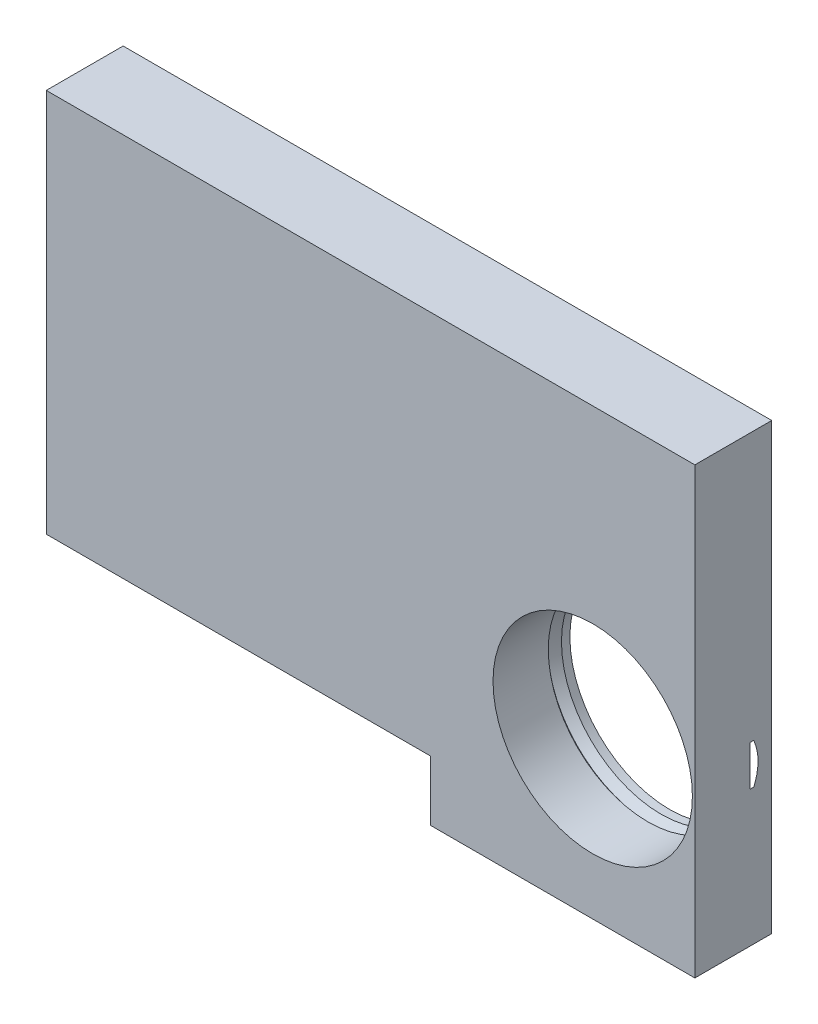
SolidWorks part; units mm, degrees
material "ABS"
ref_plane "Front Plane" through (0, 0, 0) normal (0, 0, 1) x (1, 0, 0)
ref_plane "Top Plane" through (0, 0, 0) normal (0, 1, 0) x (1, 0, 0)
ref_plane "Right Plane" through (0, 0, 0) normal (1, 0, 0) x (0, 0, -1)
sketch "Sketch1" plane through (0, 0, 17.5436) normal (0, 0, 1) x (1, 0, 0)
  line L0 (-2.5012, -56.5) -> (-2.5012, -59)
  line L1 (-2.5012, -59) -> (8.4988, -59)
  line L2 (8.4988, -59) -> (8.4988, -40.5)
  line L3 (8.4988, -40.5) -> (-2.5012, -40.5)
  line L4 (-2.5012, -40.5) -> (-18.5012, -40.5)
  line L5 (-18.5012, -40.5) -> (-18.5012, -56.5)
  line L6 (-18.5012, -56.5) -> (-2.5012, -56.5)
  line L7 (-2.5012, -56.5) -> (-2.5012, -40.5)
  line L8 (-2.5012, -40.5) -> (-18.5012, -40.5)
  line L9 (-18.5012, -40.5) -> (-18.5012, -56.5)
  line L10 (-18.5012, -56.5) -> (-2.5012, -56.5)
  line L11 (-2.5012, -56.5) -> (-2.5012, -40.5)
  circle A0 centre (4.2462, -52.5) radius 4 construction
  circle A1 centre (-6.5262, -52.475) radius 2.425 construction
  circle A2 centre (-6.5262, -44.525) radius 2.425 construction
  circle A3 centre (-14.4762, -44.525) radius 2.425 construction
  circle A4 centre (-14.4762, -52.475) radius 2.425 construction
  circle A5 centre (4.2462, -52.5) radius 4 construction
  circle A6 centre (-6.5262, -52.475) radius 2.425 construction
  circle A7 centre (-6.5262, -44.525) radius 2.425 construction
  circle A8 centre (-14.4762, -44.525) radius 2.425 construction
  circle A9 centre (-14.4762, -52.475) radius 2.425 construction
  circle A10 centre (4.2462, -52.5) radius 4.15
  circle A11 centre (-14.4762, -44.525) radius 2.575
  circle A12 centre (-6.5262, -44.525) radius 2.575
  circle A13 centre (-6.5262, -52.475) radius 2.575
  circle A14 centre (-14.4762, -52.475) radius 2.575
  line M11 (-2.5012, -40.5) -> (-18.5012, -40.5)
  line M12 (-18.5012, -40.5) -> (-18.5012, -56.5)
  line M13 (-18.5012, -56.5) -> (-2.5012, -56.5)
  line M14 (-2.5012, -56.5) -> (-2.5012, -40.5)
  dimension "D3" = 0.15
  dimension "D4" = 11
  dimension "D5" = 18.5
  dimension "D1" = 0
  dimension "D2" = 0.15
extrude "Boss-Extrude1" add sketch "Sketch1" along normal blind 3.2 contours L2 L3 L0 L1 A10 M14 | A14 A13 A12 A11 M14 M11 M12 M13 | A13 | A12 | A14 | A11 region at (-2.2859, -48.5, 17.5436) region at (-10.5012, -48.5, 17.5436)
sketch "Sketch2" plane through (4.2462, -52.5, 15.4436) normal (0, 1, 0) x (1, 0, 0)
  line L0 (-4.235, -2.9) -> (4.235, -2.9) construction
  line L1 (-4, -2.365) -> (4, -2.365) construction
  line L2 (4, -2.365) -> (-4, -2.365) construction
  line L3 (-4.235, -2.9) -> (4.235, -2.9) construction
  line L4 (-4, -2.365) -> (4, -2.365) construction
  line L5 (4, -2.365) -> (-4, -2.365) construction
  line L6 (-4, -2.9) -> (-4.235, -2.9)
  line L7 (-4.235, -2.9) -> (-4.235, -2.869)
  line L8 (-4.235, -2.869) -> (-4, -2.365)
  line L9 (-4, -2.365) -> (-4, -2.9)
  line L10 (-3.9, -1.9139) -> (-3.9, -3)
  line L11 (-3.9, -3) -> (-4.335, -3)
  line L12 (-4.335, -3) -> (-4.335, -2.8468)
  line L13 (-4.335, -2.8468) -> (-3.9, -1.9139)
  line L14 (0, -2.9) -> (0, 49997.1) construction
  point P13 (0, -2.9)
  dimension "D1" = 0.1
revolve "Cut-Revolve1" cut sketch "Sketch2" angle 360 about L14
extrude "Cut-Extrude1" cut sketch "Sketch1<3>" along normal blind 1.8 contours A11 | A14 | A13 | A12
sketch "Sketch1<3>" plane through (0, 0, 17.5436) normal (0, 0, 1) x (1, 0, 0) same geometry as "Sketch1"
